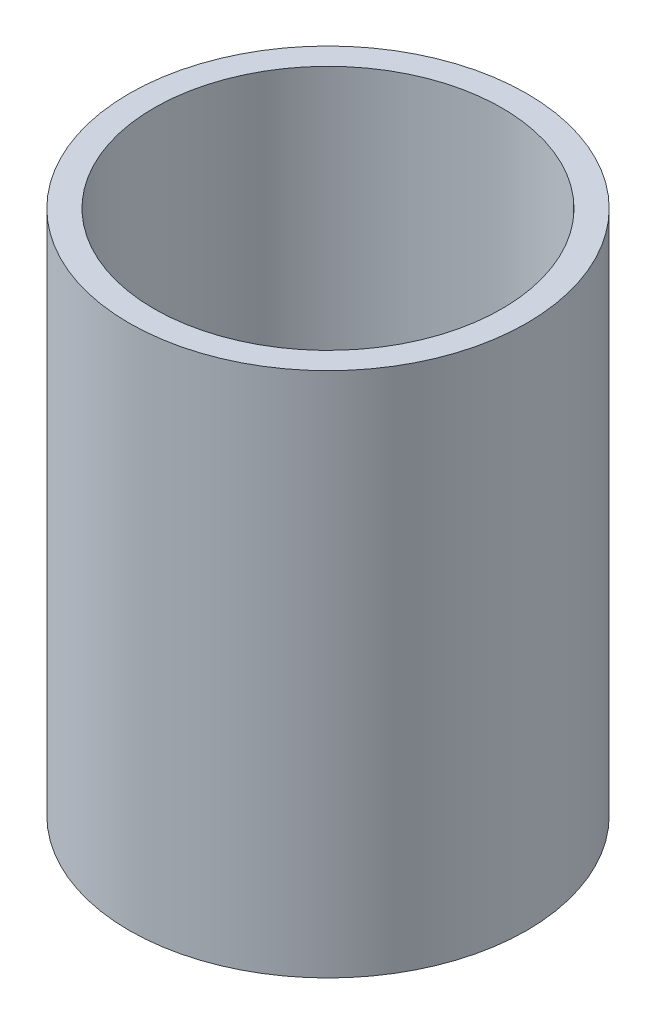
SolidWorks part; units mm, degrees
ref_plane "Front Plane" through (0, 0, 0) normal (0, 0, 1) x (1, 0, 0)
ref_plane "Top Plane" through (0, 0, 0) normal (0, 1, 0) x (1, 0, 0)
ref_plane "Right Plane" through (0, 0, 0) normal (1, 0, 0) x (0, 0, -1)
sketch "Sketch1" plane through (0, 0, 0) normal (0, 1, 0) x (1, 0, 0)
  circle A0 centre (0, 0) radius 30
  dimension "SLEEVE_OD" = 60
extrude "Boss-Extrude1" add sketch "Sketch1" along normal blind 79.3534
sketch "Sketch2" plane through (0, 0, 0) normal (0, 1, 0) x (1, 0, 0)
  circle A0 centre (0, 0) radius 26.2497
  dimension "BORE_D" = 52.4993
extrude "Cut-Extrude1" cut sketch "Sketch2" along normal through all
chamfer "Chamfer1" distance 2.1717 angle 60 rebuild error yes
